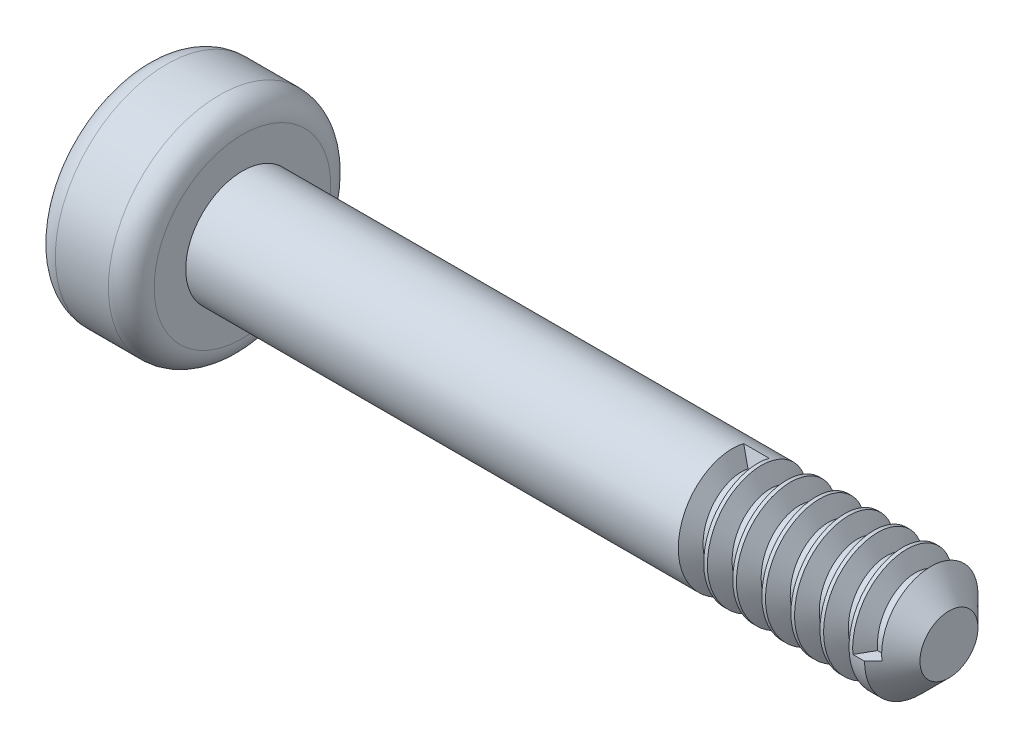
SolidWorks part; units mm, degrees
material "1060 Alloy"
ref_plane "Front Plane" through (0, 0, 0) normal (0, 0, 1) x (1, 0, 0)
ref_plane "Top Plane" through (0, 0, 0) normal (0, 1, 0) x (1, 0, 0)
ref_plane "Right Plane" through (0, 0, 0) normal (1, 0, 0) x (0, 0, -1)
sketch "Sketch2" plane through (0, 0, 0) normal (0, 0, 1) x (1, 0, 0)
  line L0 (0, 0) -> (-50000, 0) construction
  line L1 (0, 0) -> (0, 0.965)
  line L2 (0.25, 1.215) -> (0.83, 1.215)
  line L3 (8.8, 0) -> (8.8, 0.62)
  line L4 (1.58, 0.62) -> (1.08, 0.62)
  line L5 (1.08, 0.62) -> (8.8, 0.62) construction
  line L6 (0, 0) -> (8.8, 0)
  line L7 (8.8, 0.62) -> (5.8, 0.62)
  line L9 (1.08, 0.62) -> (1.08, 0.965)
  line L10 (5.8, 0.62) -> (1.58, 0.62)
  arc A0 (0, 0.965) -> (0.25, 1.215) centre (0.25, 0.965) cw
  arc A1 (1.08, 0.965) -> (0.83, 1.215) centre (0.83, 0.965) ccw
  dimension "D1" = 0.25
  dimension "D3" = 0.25
  dimension "D4" = 3
  dimension "D2" = 0.62
  dimension "D5" = 0.62
revolve "Revolve1" add sketch "Sketch2" angle 360 about L0
sketch "Sketch5" plane through (0, 0, 0) normal (-1, 0, 0) x (0, 0, 1)
  line L0 (0.755, 0) -> (-0.755, 0) construction
  line L1 (0, 0.755) -> (0, -0.755) construction
  line L2 (0.2, 0.755) -> (-0.2, 0.755)
  line L3 (0.2, -0.755) -> (-0.2, -0.755)
  line L4 (-0.755, 0.2) -> (-0.755, -0.2)
  line L5 (0.755, 0.2) -> (0.755, -0.2)
  line L6 (-0.2, 0.755) -> (-0.2, 0.2)
  line L7 (-0.2, 0.2) -> (-0.755, 0.2)
  line L8 (-0.755, -0.2) -> (-0.2, -0.2)
  line L9 (-0.2, -0.2) -> (-0.2, -0.755)
  line L10 (0.2, 0.755) -> (0.2, 0.2)
  line L11 (0.2, 0.2) -> (0.755, 0.2)
  line L12 (0.2, -0.755) -> (0.2, -0.2)
  line L13 (0.2, -0.2) -> (0.755, -0.2)
  point P5 (0, 0)
  point P8 (0, 0)
  point P11 (0, 0.755)
  point P16 (-0.755, 0)
extrude "Cut-Extrude1" cut sketch "Sketch5" against normal blind 0.5
sketch "Sketch6" plane through (0, 0, 0) normal (0, 0, 1) x (1, 0, 0)
  line L0 (8.8, -0.3171) -> (8.4971, -0.62)
  line L1 (8.8, -0.62) -> (8.8, 0.62) construction
  line L2 (1.08, -0.62) -> (8.8, -0.62) construction
  line L3 (8.8, -0.3171) -> (8.8, -0.62)
  line L4 (8.8, -0.62) -> (8.4971, -0.62)
  line L5 (-0.2088, 0) -> (9.0906, 0) construction
revolve "Cut-Revolve1" cut sketch "Sketch6" angle 360 about L5
thread "Thread1" pitch 0.3175 method cut profile "Thread Profile1" start angle 0, offset 0.15, length 2, pitch 0.3175, diameter 1.24
ref_plane "Plane1" through (8.6471, 0, 0.62) normal (0, -1, 0) x (0, 0, 1)
sketch "Thread Profile1" plane through (8.6471, 0, 0.62) normal (0, -1, 0) x (0, 0, 1)
  line L0 (0, 0) -> (0, 0.3175) construction
  line L11 (0, 0) -> (0, 0.2778)
  line L12 (0, 0.2778) -> (-0.1719, 0.1786)
  line L13 (-0.1719, 0.1786) -> (-0.1719, 0.0992)
  line L15 (-0.1719, 0.0992) -> (0, 0)
  line L17 (-0.1719, 0.1389) -> (0, 0.1389) construction
  point P2 (0, 0)
  dimension "Pitch" = 0.3175
  dimension "Profile_Angle" = 60
  dimension "Profile_Land" = 0.0794
  dimension "Profile_Height" = 0.1719
